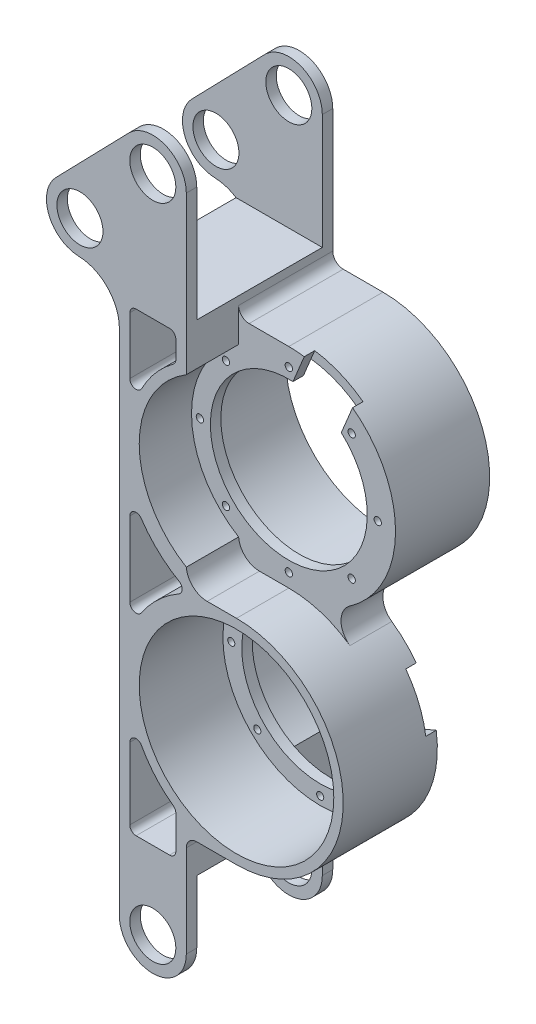
SolidWorks part; units mm, degrees
material "6061 合金"
ref_plane "前视基准面" through (0, 0, 0) normal (0, 0, 1) x (1, 0, 0)
ref_plane "上视基准面" through (0, 0, 0) normal (0, 1, 0) x (1, 0, 0)
ref_plane "右视基准面" through (0, 0, 0) normal (1, 0, 0) x (0, 0, -1)
other "Configuration Table"
sketch "草图1" plane through (0, 0, 0) normal (0, 0, 1) x (1, 0, 0)
  line L0 (0, 0) -> (0, 332.8631) construction
  line L1 (0, 315) -> (-34.8395, 279.1362) construction
  line L2 (110, 299.7268) -> (110, -14.6739) construction
  line L3 (-11.4764, 326.1486) -> (-46.3159, 290.2849)
  line L5 (-34.8395, 263.1362) -> (-16, 263.1362)
  line L6 (-16, 263.1362) -> (-16, 0)
  line L8 (16, 0) -> (16, 49)
  line L9 (16, 49) -> (40, 49)
  line L10 (91, 100) -> (91, 200)
  line L11 (40, 251) -> (16, 251)
  line L12 (16, 251) -> (16, 315)
  circle A0 centre (0, 315) radius 11
  circle A1 centre (0, 0) radius 11
  circle A2 centre (-34.8395, 279.1362) radius 11
  circle A3 centre (40, 200) radius 46 construction
  circle A4 centre (40, 100) radius 46 construction
  arc A5 (16, 315) -> (-11.4764, 326.1486) centre (0, 315) ccw
  arc A6 (-46.3159, 290.2849) -> (-34.8395, 263.1362) centre (-34.8395, 279.1362) ccw
  arc A7 (-16, 0) -> (16, 0) centre (0, 0) ccw
  arc A10 (40, 251) -> (91, 200) centre (40, 200) cw
  arc A11 (91, 100) -> (40, 49) centre (40, 100) cw
  point P24 (16, 283)
  dimension "D1" = 22
  dimension "D5" = 92
  dimension "D2" = 315
  dimension "D3" = 44.17
  dimension "D4" = 50
  dimension "D6" = 110
  dimension "D7" = 40
  dimension "D8" = 100
  dimension "D9" = 200
  dimension "D10" = 16
  dimension "D11" = 16
  dimension "D12" = 16
  dimension "D13" = 16
  dimension "D14" = 16
  dimension "D15" = 51
  dimension "D16" = 51
  dimension "D17" = 51
extrude "凸台-拉伸1" add sketch "草图1" along normal blind 70
fillet "圆角1" radius 5 2 edges at (16, 49, 35) (16, 251, 35)
sketch "草图2" plane through (0, 0, 70) normal (0, 0, 1) x (1, 0, 0)
  circle A0 centre (40, 100) radius 46.5
  dimension "D1" = 93
extrude "切除-拉伸1" cut sketch "草图2" against normal blind 40
sketch "草图3" plane through (0, 0, 0) normal (0, 0, -1) x (-1, 0, 0)
  circle A0 centre (-40, 200) radius 46.5
  dimension "D1" = 93
extrude "切除-拉伸2" cut sketch "草图3" against normal blind 40
sketch "草图4" plane through (0, 0, 0) normal (0, 0, -1) x (-1, 0, 0)
  line L0 (-16, 0) -> (-16, 49) construction
  line L1 (-16, 44) -> (-16, 49)
  line L2 (-16, 49) -> (-16, 149)
  line L3 (-16, 149) -> (-40, 149)
  line L4 (-16, 49) -> (-40, 49) construction
  line L5 (-91, 100) -> (-91, 200) construction
  line L6 (-21, 49) -> (-40, 49)
  line L7 (-91, 100) -> (-91, 200)
  arc A0 (-91, 200) -> (-40, 149) centre (-40, 200) ccw
  arc A1 (-16, 44) -> (-21, 49) centre (-21, 44) ccw construction
  arc A2 (-91, 100) -> (-40, 49) centre (-40, 100) ccw construction
  arc A3 (-16, 44) -> (-21, 49) centre (-21, 44) ccw
  arc A4 (-91, 100) -> (-40, 49) centre (-40, 100) ccw
extrude "切除-拉伸3" cut sketch "草图4" against normal blind 25
sketch "草图5" plane through (0, 0, 70) normal (0, 0, 1) x (1, 0, 0)
  line L0 (16, 251) -> (16, 315) construction
  line L1 (16, 251) -> (16, 256)
  line L2 (16, 251) -> (16, 151)
  line L3 (16, 151) -> (40, 151)
  line L4 (91, 100) -> (91, 200) construction
  line L5 (40, 251) -> (16, 251) construction
  line L6 (91, 100) -> (91, 200)
  line L7 (40, 251) -> (21, 251)
  arc A0 (91, 100) -> (40, 151) centre (40, 100) ccw
  arc A1 (91, 200) -> (40, 251) centre (40, 200) ccw construction
  arc A2 (16, 256) -> (21, 251) centre (21, 256) ccw construction
  arc A3 (91, 200) -> (40, 251) centre (40, 200) ccw
  arc A4 (16, 256) -> (21, 251) centre (21, 256) ccw
extrude "切除-拉伸4" cut sketch "草图5" against normal blind 25
sketch "草图6" plane through (0, 0, 45) normal (0, 0, 1) x (1, 0, 0)
  line L0 (91, 100) -> (91, 200) construction
  line L1 (91, 100) -> (91, 200)
  arc A0 (50.0499, 150) -> (91, 200) centre (40, 200) ccw
  arc A1 (40, 49) -> (40, 151) centre (40, 100) ccw construction
  arc A2 (91, 100) -> (50.0499, 150) centre (40, 100) ccw
extrude "切除-拉伸5" cut sketch "草图6" against normal blind 30
fillet "圆角2" radius 10 1 edges at (50.0499, 150, 35)
sketch "草图8" plane through (0, 0, 30) normal (0, 0, 1) x (1, 0, 0)
  circle A0 centre (40, 100) radius 37.5
  circle A1 centre (40, 200) radius 37.5
  dimension "D1" = 75
extrude "切除-拉伸6" cut sketch "草图8" against normal through all both and the other way through all
sketch "草图9" plane through (16, 0, 0) normal (1, 0, 0) x (0, 0, -1)
  line L0 (-35, 23.9908) -> (-35, -35.971) construction
  line L1 (0, 263.1362) -> (0, 0) construction
  line L2 (-70, 0) -> (-70, 44) construction
  line L4 (-65, 30) -> (-5, 30)
  line L5 (-65, 30) -> (-65, -30)
  line L6 (-65, -30) -> (-5, -30)
  line L7 (-5, 30) -> (-5, -30)
  line L8 (-65, 360) -> (-5, 360)
  line L9 (-65, 360) -> (-65, 260)
  line L10 (-65, 260) -> (-5, 260)
  line L11 (-5, 360) -> (-5, 260)
  dimension "D1" = 60
  dimension "D2" = 30
  dimension "D3" = 60
  dimension "D4" = 260
  dimension "D5" = 100
extrude "切除-拉伸7" cut sketch "草图9" against normal through all both
sketch "草图10" plane through (0, 0, 70) normal (0, 0, 1) x (1, 0, 0)
  line L0 (-11, 92.8411) -> (-11, 37)
  line L1 (-11, 37) -> (11, 37)
  line L2 (11, 37) -> (11, 57.4412)
  line L3 (-16, 263.1362) -> (-16, 0) construction
  line L4 (16, 0) -> (16, 49) construction
  circle A0 centre (40, 100) radius 46.5 construction
  circle A1 centre (40, 100) radius 46.5 construction
  arc A2 (-11, 92.8411) -> (11, 57.4412) centre (40, 100) ccw
  dimension "D1" = 5
  dimension "D2" = 5
  dimension "D3" = 5
  dimension "D4" = 37
extrude "切除-拉伸8" cut sketch "草图10" against normal through all both
sketch "草图11" plane through (0, 0, 0) normal (0, 0, -1) x (-1, 0, 0)
  line L0 (-11, 255) -> (11, 255)
  line L1 (11, 255) -> (11, 200)
  line L2 (-11, 255) -> (-11, 241.9524)
  line L3 (16, 263.1362) -> (16, 0) construction
  line L4 (-16, 251) -> (-16, 315) construction
  arc A0 (11, 200) -> (-11, 241.9524) centre (-40, 200) ccw
  circle A1 centre (-40, 200) radius 46 construction
  dimension "D4" = 5
  dimension "D1" = 5
  dimension "D2" = 5
  dimension "D3" = 55
extrude "切除-拉伸9" cut sketch "草图11" against normal through all both
fillet "圆角3" radius 20 1 edges at (-16, 263.1362, 67.5)
fillet "圆角4" radius 3 8 edges at (-11, 255, 35) (-11, 200, 35) (11, 241.9524, 35) (11, 255, 35) (11, 37, 35) (-11, 37, 35) (-11, 92.8411, 35) (11, 57.4412, 35)
sketch "草图12" plane through (0, 0, 0) normal (0, 0, -1) x (-1, 0, 0)
  circle A0 centre (-40, 100) radius 46.5 construction
  circle A1 centre (-40, 100) radius 46.5
extrude "切除-拉伸10" cut sketch "草图12" against normal up to surface (25 mm away) up to face at (43.8186, 103.1195, 25)
sketch "草图13" plane through (0, 0, 70) normal (0, 0, 1) x (1, 0, 0)
  circle A0 centre (40, 200) radius 46.5 construction
  circle A1 centre (40, 200) radius 46.5
extrude "切除-拉伸11" cut sketch "草图13" against normal up to surface (25 mm away) up to face at (43.8186, 196.8805, 45)
sketch "草图14" plane through (0, 0, 70) normal (0, 0, 1) x (1, 0, 0)
  line L0 (-11, 180) -> (-11, 120)
  line L1 (-16, 243.1549) -> (-16, 0) construction
  line L2 (-83.0275, 150) -> (17.617, 150) construction
  line L3 (62.383, 150) -> (169.8304, 150) construction
  arc A0 (-11, 180) -> (17.617, 150) centre (40, 200) ccw
  arc A1 (17.617, 150) -> (-11, 120) centre (40, 100) ccw
  point P12 (0, 0)
  point P13 (-11, 189.7158)
  point P14 (0, 0)
  point P15 (-11, 122.4682)
  dimension "D1" = 5
  dimension "D2" = 60
extrude "切除-拉伸12" cut sketch "草图14" against normal through all both and the other way through all
fillet "圆角5" radius 10 2 edges at (16, 151, 57.5) (16, 149, 12.5)
fillet "圆角6" radius 3 3 edges at (-11, 120, 35) (17.617, 150, 35) (-11, 180, 35)
sketch "草图15" plane through (0, 0, 30) normal (0, 0, 1) x (1, 0, 0)
  line L0 (40, 200) -> (40, 281.792) construction
  line L1 (40, 100) -> (40, 146.5) construction
  circle A0 centre (40, 100) radius 42.5 construction
  circle A1 centre (40, 200) radius 42.5 construction
  circle A2 centre (40, 242.5) radius 1.75
  circle A3 centre (70.052, 230.052) radius 1.75
  circle A4 centre (82.5, 200) radius 1.75
  circle A5 centre (70.052, 169.948) radius 1.75
  circle A6 centre (40, 157.5) radius 1.75
  circle A7 centre (9.948, 169.948) radius 1.75
  circle A8 centre (-2.5, 200) radius 1.75
  circle A9 centre (9.948, 230.052) radius 1.75
  circle A10 centre (40, 100) radius 46.5 construction
  circle A11 centre (40, 142.5) radius 1.7
  circle A12 centre (70.052, 130.052) radius 1.7
  circle A13 centre (82.5, 100) radius 1.7
  circle A14 centre (70.052, 69.948) radius 1.7
  circle A15 centre (40, 57.5) radius 1.7
  circle A16 centre (9.948, 69.948) radius 1.7
  circle A17 centre (-2.5, 100) radius 1.7
  circle A18 centre (9.948, 130.052) radius 1.7
  point P25 (40, 200)
  point P31 (40, 100)
  point P46 (40, 100)
  dimension "D1" = 85
  dimension "D2" = 3.5
  dimension "D4" = 3.4
  dimension "D3" = 8
  dimension "D5" = 8
extrude "切除-拉伸13" cut sketch "草图15" against normal through all both and the other way through all
sketch "草图16" plane through (0, 0, 25) normal (0, 0, -1) x (-1, 0, 0)
  line L0 (-40, 100) -> (-124.0108, 134.7984) construction
  line L1 (-98.2455, 137.656) -> (-107.8126, 114.559)
  line L2 (-107.8126, 114.559) -> (-68.7541, 98.3804)
  line L3 (-68.7541, 98.3804) -> (-59.187, 121.4774)
  line L4 (-59.187, 121.4774) -> (-98.2455, 137.656)
  circle A0 centre (-70.052, 130.052) radius 1.7 construction
  circle A1 centre (-82.5, 100) radius 1.7 construction
  dimension "D1" = 25
extrude "切除-拉伸14" cut sketch "草图16" against normal blind 5
sketch "草图17" plane through (0, 0, 45) normal (0, 0, 1) x (1, 0, 0)
  line L0 (40, 200) -> (72.1716, 277.6691) construction
  line L1 (55.3339, 269.6834) -> (39.6525, 231.8251)
  line L2 (39.6525, 231.8251) -> (62.7495, 222.258)
  line L3 (62.7495, 222.258) -> (78.4309, 260.1163)
  line L4 (78.4309, 260.1163) -> (55.3339, 269.6834)
  circle A0 centre (70.052, 230.052) radius 1.75 construction
  circle A1 centre (40, 242.5) radius 1.75 construction
  dimension "D1" = 25
extrude "切除-拉伸15" cut sketch "草图17" against normal blind 5
